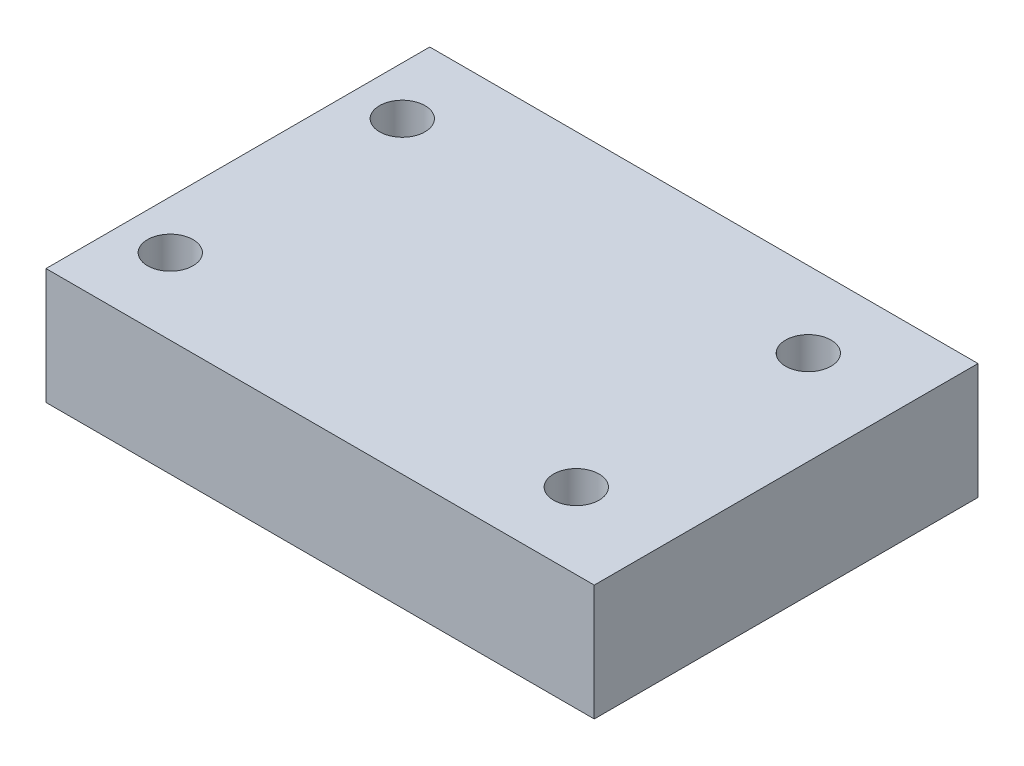
SolidWorks part; units mm, degrees
ref_plane "Front Plane" through (0, 0, 0) normal (0, 0, 1) x (1, 0, 0)
ref_plane "Top Plane" through (0, 0, 0) normal (0, 1, 0) x (1, 0, 0)
ref_plane "Right Plane" through (0, 0, 0) normal (1, 0, 0) x (0, 0, -1)
sketch "Sketch1" plane through (0, 0, 0) normal (0, 1, 0) x (1, 0, 0)
  line L0 (-30.0101, 0) -> (30.0101, 0) construction
  line L1 (0, -21.0058) -> (0, 21.0058) construction
  line L7 (-30.0101, 21.0058) -> (30.0101, 21.0058)
  line L8 (-30.0101, 21.0058) -> (-30.0101, -21.0058)
  line L9 (-30.0101, -21.0058) -> (30.0101, -21.0058)
  line L10 (30.0101, 21.0058) -> (30.0101, -21.0058)
  line L11 (-30.0101, 21.0058) -> (30.0101, -21.0058) construction
  line L12 (-30.0101, -21.0058) -> (30.0101, 21.0058) construction
  point P0 (0, 0)
extrude "Boss-Extrude1" add sketch "Sketch1" along normal blind 12.7
sketch "Sketch2" plane through (0, 12.7, 0) normal (0, 1, 0) x (1, 0, 0)
  line L0 (-30.0101, 21.0058) -> (-24.7101, 21.0058) construction
  line L1 (30.0101, 21.0058) -> (-30.0101, 21.0058) construction
  line L2 (-24.7101, 21.0058) -> (-24.7101, 12.7) construction
  line L4 (-24.7101, 12.7) -> (19.7399, 12.7) construction
  line L5 (-24.7101, 12.7) -> (-24.7101, -12.7) construction
  line L6 (-24.7101, -12.7) -> (19.7399, -12.7) construction
  line L7 (19.7399, 12.7) -> (19.7399, -12.7) construction
  dimension "D1" = 5.3
  dimension "D2" = 8.3058
  dimension "D3" = 25.4
hole_wizard "#10 Clearance Hole1" positions "Sketch3" profile "Sketch4" hole size "#10" standard "ANSI Inch" end condition through all
sketch "Sketch3" plane through (0, 12.7, 0) normal (0, 1, 0) x (1, 0, 0)
  point P0 (-24.7101, 12.7)
  point P3 (-24.7101, -12.7)
  point P6 (19.7399, -12.7)
  point P9 (19.7399, 12.7)
sketch "Sketch4" plane through (-24.7101, 12.7, -12.7) normal (1, 0, 0) x (0, 0, 1)
  line L0 (0, 0) -> (0, 12.7)
  line L1 (0, 12.7) -> (2.4892, 12.7)
  line L2 (2.4892, 12.7) -> (2.4892, 0)
  line L5 (2.4892, 0) -> (0, 0)
  line L11 (0, -6.35) -> (0, 107.95) construction
  dimension "Thru Hole Dia." = 4.9784
  dimension "Thru Hole Depth" = 12.7
